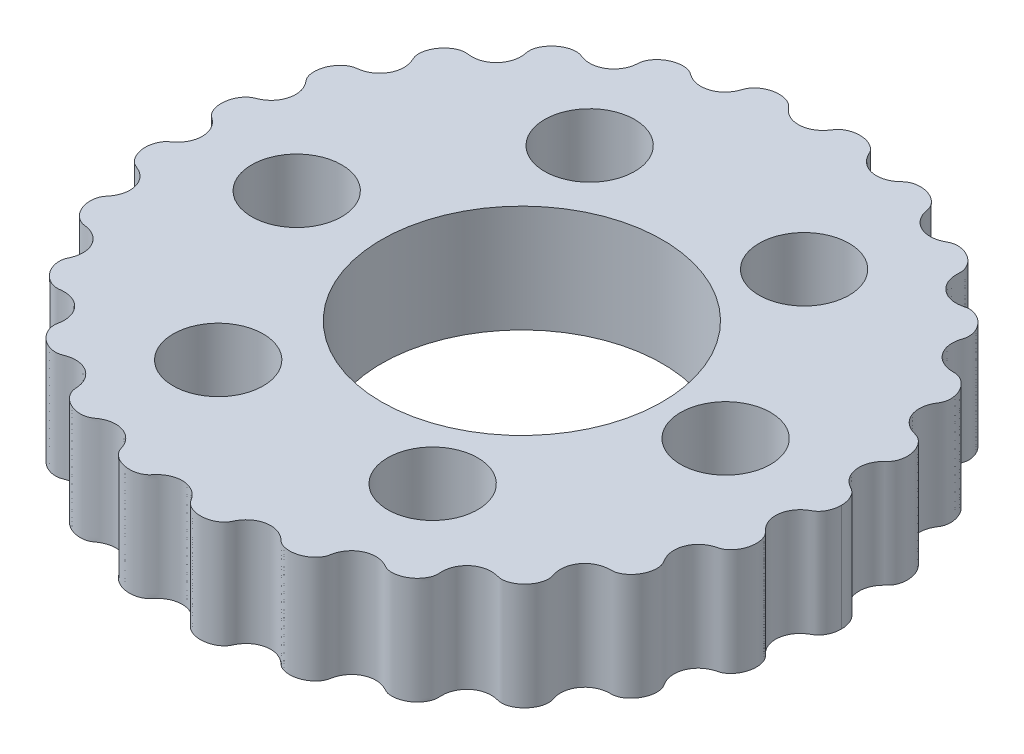
SolidWorks part; units mm, degrees
ref_plane "Front Plane" through (0, 0, 0) normal (0, 0, 1) x (1, 0, 0)
ref_plane "Top Plane" through (0, 0, 0) normal (0, 1, 0) x (1, 0, 0)
ref_plane "Right Plane" through (0, 0, 0) normal (1, 0, 0) x (0, 0, -1)
sketch "Sketch1" plane through (0, 0, 0) normal (0, 1, 0) x (1, 0, 0)
  line L0 (-15.4, 0) -> (14.4, 0) construction
  line L1 (0, 0) -> (0, 14.9128) construction
  line L2 (0, 0) -> (0, -14.9128) construction
  line L3 (0, 0) -> (-0.5, 0) construction
  line L4 (-0.5, 0) -> (-0.5, 15.3103) construction
  line L5 (-0.5, 0) -> (-0.5, -15.3103) construction
  line L6 (14.4, 0) -> (15.5, 0) construction
  line L7 (0, 0) -> (10, 0) construction
  line L8 (7.9, 0) -> (9.5, 0)
  line L9 (-0.5, 0) -> (9.5, 0) construction
  line L10 (-0.5, 15.3103) -> (-0.5, -15.3103) construction
  circle A0 centre (-0.5, 0) radius 16
  circle A1 centre (15.5, 0) radius 1
  circle A2 centre (15.0351, -3.8291) radius 1
  circle A3 centre (13.6673, -7.4356) radius 1
  circle A4 centre (11.4762, -10.61) radius 1
  circle A5 centre (8.589, -13.1677) radius 1
  circle A6 centre (5.1737, -14.9603) radius 1
  circle A7 centre (1.4286, -15.8833) radius 1
  circle A8 centre (-2.4286, -15.8833) radius 1
  circle A9 centre (-6.1737, -14.9603) radius 1
  circle A10 centre (-9.589, -13.1677) radius 1
  circle A11 centre (-12.4762, -10.61) radius 1
  circle A12 centre (-14.6673, -7.4356) radius 1
  circle A13 centre (-16.0351, -3.8291) radius 1
  circle A14 centre (-16.5, 0) radius 1
  circle A15 centre (-16.0351, 3.8291) radius 1
  circle A16 centre (-14.6673, 7.4356) radius 1
  circle A17 centre (-12.4762, 10.61) radius 1
  circle A18 centre (-9.589, 13.1677) radius 1
  circle A19 centre (-6.1737, 14.9603) radius 1
  circle A20 centre (-2.4286, 15.8833) radius 1
  circle A21 centre (1.4286, 15.8833) radius 1
  circle A22 centre (5.1737, 14.9603) radius 1
  circle A23 centre (8.589, 13.1677) radius 1
  circle A24 centre (11.4762, 10.61) radius 1
  circle A25 centre (13.6673, 7.4356) radius 1
  circle A26 centre (15.0351, 3.8291) radius 1
  circle A27 centre (0, 0) radius 10
  circle A28 centre (10, 0) radius 2.1
  circle A29 centre (5, -8.6603) radius 2.1
  circle A30 centre (-5, -8.6603) radius 2.1
  circle A31 centre (-10, 0) radius 2.1
  circle A32 centre (-5, 8.6603) radius 2.1
  circle A33 centre (5, 8.6603) radius 2.1
  circle A34 centre (-6, 8.6603) radius 2.1
  circle A35 centre (4, 8.6603) radius 2.1
  circle A36 centre (9, 0) radius 2.1
  circle A37 centre (4, -8.6603) radius 2.1
  circle A38 centre (-6, -8.6603) radius 2.1
  circle A39 centre (-1, 0) radius 10
  circle A40 centre (-11, 0) radius 2.1
  circle A41 centre (9.5, 0) radius 1.5
  circle A42 centre (4.5, -8.6603) radius 1.5
  circle A43 centre (-5.5, -8.6603) radius 1.5
  circle A44 centre (-10.5, 0) radius 1.5
  circle A45 centre (-5.5, 8.6603) radius 1.5
  circle A46 centre (4.5, 8.6603) radius 1.5
  circle A47 centre (-0.5, 0) radius 5.55
  spline S0 degree 4 number of poles 369 (14.1521, 3.1658) -> (-14.9531, 3.4358) construction
  spline S1 degree 4 number of poles 315 (14.4, 0) -> (-15.4, 0)
  spline S2 degree 4 number of poles 315 (14.4, 0) -> (-15.4, 0)
  spline S3 degree 4 number of poles 315 (-15.4, 0) -> (14.4, 0)
  spline S4 degree 4 number of poles 315 (-15.4, 0) -> (14.4, 0)
  dimension "D1" = 32
  dimension "D2" = 2
  dimension "D4" = 20
  dimension "D5" = 4.2
  dimension "D8" = 6
  dimension "D7" = 10
  dimension "D9" = 10
  dimension "D3" = 26
  dimension "D6" = 6
sketch "Sketch2" plane through (0, 0, 0) normal (0, 1, 0) x (1, 0, 0)
  spline S0 degree 4 number of poles 315 (-15.4, 0) -> (14.4, 0)
  spline S1 degree 4 number of poles 315 (-15.4, 0) -> (14.4, 0)
extrude "Boss-Extrude2" add sketch "Sketch2" against normal blind 5
sketch "Sketch3" plane through (0, 0, 0) normal (0, 1, 0) x (1, 0, 0)
  circle A0 centre (-6, 8.6603) radius 2.1
  circle A1 centre (4, 8.6603) radius 2.1
  circle A2 centre (9, 0) radius 2.1
  circle A3 centre (4, -8.6603) radius 2.1
  circle A4 centre (-6, -8.6603) radius 2.1
  circle A5 centre (-11, 0) radius 2.1
extrude "Cut-Extrude1" cut sketch "Sketch3" against normal through all
sketch "Sketch4" plane through (0, 0, 0) normal (0, 1, 0) x (1, 0, 0)
  circle A0 centre (-0.5, 0) radius 5.55
sketch "Sketch5" plane through (0, 0, 0) normal (0, 1, 0) x (1, 0, 0)
  circle A0 centre (-0.5, 0) radius 6.55
  dimension "D1" = 13.1
extrude "Cut-Extrude3" cut sketch "Sketch5" against normal through all
